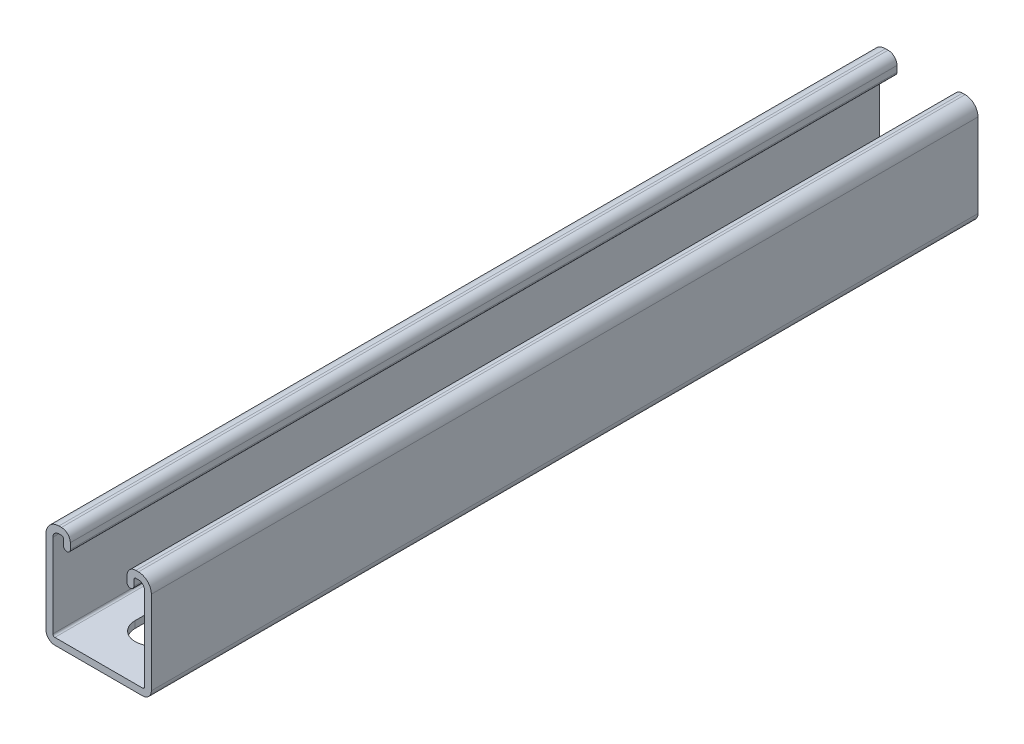
SolidWorks part; units mm, degrees
ref_plane "Front Plane" through (0, 0, 0) normal (0, 0, 1) x (1, 0, 0)
ref_plane "Top Plane" through (0, 0, 0) normal (0, 1, 0) x (1, 0, 0)
ref_plane "Right Plane" through (0, 0, 0) normal (1, 0, 0) x (0, 0, -1)
ref_plane "Plane1" through (0, 0, 3048) normal (0, 0, 1) x (1, 0, 0)
sketch "Sketch1" plane through (0, 0, 0) normal (0, 0, 1) x (1, 0, 0)
  line L0 (-20.6377, 0) -> (-17.9706, 0) construction
  line L1 (20.6377, 0) -> (17.9706, 0) construction
  line L2 (17.1769, -17.9704) -> (-17.1769, -17.9704)
  line L3 (-17.9706, -17.1766) -> (-17.9706, 15.5891)
  line L4 (-15.5894, 17.9704) -> (-14.5734, 17.9704)
  line L5 (-13.7797, 17.1766) -> (-13.7797, 14.8335)
  line L6 (-11.1127, 14.8335) -> (-11.1127, 17.1766)
  line L7 (-14.5734, 20.6374) -> (-15.5894, 20.6374)
  line L8 (-20.6377, 15.5891) -> (-20.6377, -17.1766)
  line L9 (-17.1769, -20.6374) -> (17.1769, -20.6374)
  line L10 (20.6377, 15.5891) -> (20.6377, -17.1766)
  line L11 (14.5734, 20.6374) -> (15.5894, 20.6374)
  line L12 (11.1127, 14.8335) -> (11.1127, 17.1766)
  line L13 (13.7797, 17.1766) -> (13.7797, 14.8335)
  line L14 (0, -17.9704) -> (0, -20.6374) construction
  line L15 (15.5894, 17.9704) -> (14.5734, 17.9704)
  line L16 (17.9706, -17.1766) -> (17.9706, 15.5891)
  arc A0 (-17.1769, -20.6374) -> (-20.6377, -17.1766) centre (-17.1769, -17.1766) cw
  arc A1 (-17.1769, -17.9704) -> (-17.9706, -17.1766) centre (-17.1769, -17.1766) cw
  arc A2 (-17.9706, 15.5891) -> (-15.5894, 17.9704) centre (-15.5894, 15.5891) cw
  arc A3 (-20.6377, 15.5891) -> (-15.5894, 20.6374) centre (-15.5894, 15.5891) cw
  arc A4 (-14.5734, 17.9704) -> (-13.7797, 17.1766) centre (-14.5734, 17.1766) cw
  arc A5 (-14.5734, 20.6374) -> (-11.1127, 17.1766) centre (-14.5734, 17.1766) cw
  arc A6 (-13.7797, 14.8335) -> (-11.1127, 14.8335) centre (-12.4462, 14.8335) ccw
  arc A7 (13.7797, 14.8335) -> (11.1127, 14.8335) centre (12.4462, 14.8335) cw
  arc A8 (14.5734, 20.6374) -> (11.1127, 17.1766) centre (14.5734, 17.1766) ccw
  arc A9 (14.5734, 17.9704) -> (13.7797, 17.1766) centre (14.5734, 17.1766) ccw
  arc A10 (20.6377, 15.5891) -> (15.5894, 20.6374) centre (15.5894, 15.5891) ccw
  arc A11 (17.9706, 15.5891) -> (15.5894, 17.9704) centre (15.5894, 15.5891) ccw
  arc A12 (17.1769, -17.9704) -> (17.9706, -17.1766) centre (17.1769, -17.1766) ccw
  arc A13 (17.1769, -20.6374) -> (20.6377, -17.1766) centre (17.1769, -17.1766) ccw
  dimension "D4" = 3.4608
  dimension "D5" = 5.0483
  dimension "D7" = 3.4608
  dimension "D1" = 34.3538
  dimension "D2" = 41.2748
  dimension "D3" = 2.667
  dimension "D6" = 1.016
  dimension "D8" = 2.3432
extrude "Primary Extrusion" add sketch "Sketch1" against normal blind 323.85
sketch "Sketch58" plane through (0, -20.6374, 0) normal (0, 1, 0) x (-1, 0, 0)
  line L0 (7.1438, -29.3687) -> (7.1438, -21.4313)
  line L1 (-7.1438, -21.4313) -> (-7.1438, -29.3687)
  line L2 (0, 22.7012) -> (0, -22.7012) construction
  line L3 (-7.1438, -25.4) -> (7.1438, -25.4) construction
  line L4 (17.1769, 0) -> (-17.1769, 0) construction
  arc A0 (7.1438, -29.3687) -> (-7.1438, -29.3687) centre (0, -29.3687) cw
  arc A1 (-7.1438, -21.4313) -> (7.1438, -21.4313) centre (0, -21.4313) cw
  point P12 (0, -36.5125)
  point P13 (0, -14.2875)
  dimension "D2" = 22.225
  dimension "D1" = 14.2875
  dimension "D3" = 25.4
extrude "Slot Cut" cut sketch "Sketch58" along normal up to next contours L0 A1 L1 A0
pattern_linear "LPattern1" count 7 spacing 50.8 along (0, 0, -1) of "Slot Cut"
